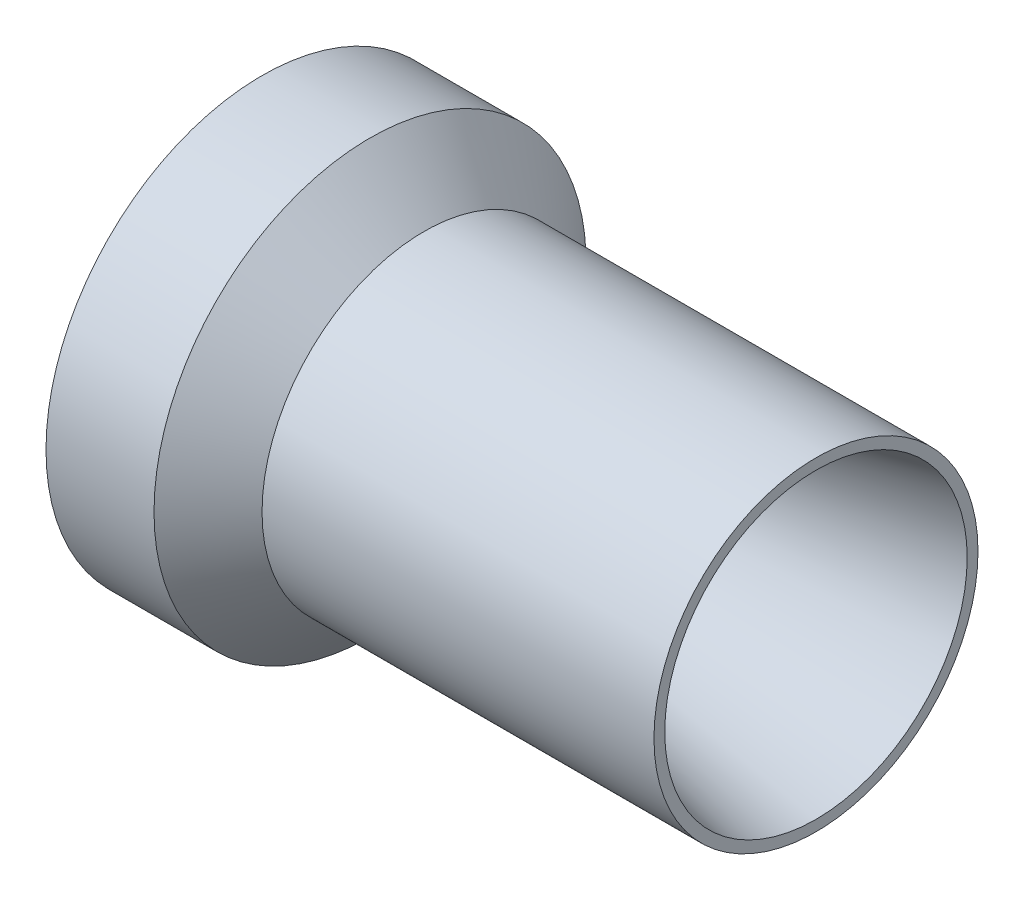
SolidWorks part; units mm, degrees
material "C (Graphite)"
ref_plane "Front Plane" through (0, 0, 0) normal (0, 0, 1) x (1, 0, 0)
ref_plane "Top Plane" through (0, 0, 0) normal (0, 1, 0) x (1, 0, 0)
ref_plane "Right Plane" through (0, 0, 0) normal (1, 0, 0) x (0, 0, -1)
sketch "Sketch1" plane through (0, 0, 0) normal (0, 0, 1) x (1, 0, 0)
  line L0 (0, 0) -> (0, 9.525)
  line L1 (130.2632, 24.765) -> (40.64, 43.815)
  line L3 (0, 60.325) -> (76.2, 60.325) construction
  line L4 (0, 9.525) -> (34.29, 43.815)
  line L5 (34.29, 43.815) -> (40.64, 43.815)
  line L6 (130.2632, 24.765) -> (130.2632, 22.225)
  line L7 (25.4, 9.525) -> (0, 9.525)
  line L9 (25.4, 9.525) -> (38.1, 22.225)
  line L12 (38.1, 22.225) -> (130.2632, 22.225)
  dimension "D1" = 60.325
  dimension "D2" = 45
  dimension "D3" = 6.35
  dimension "D4" = 25.4
  dimension "D5" = 9.525
  dimension "D6" = 12.7
  dimension "D7" = 12
  dimension "D8" = 135
  dimension "D9" = 16.51
  dimension "D11" = 92.1632
  dimension "D12" = 35.56
revolve "Revolve1" add sketch "Sketch1" angle 360 about L3 region at (54.8147, 27.2908, 0)
